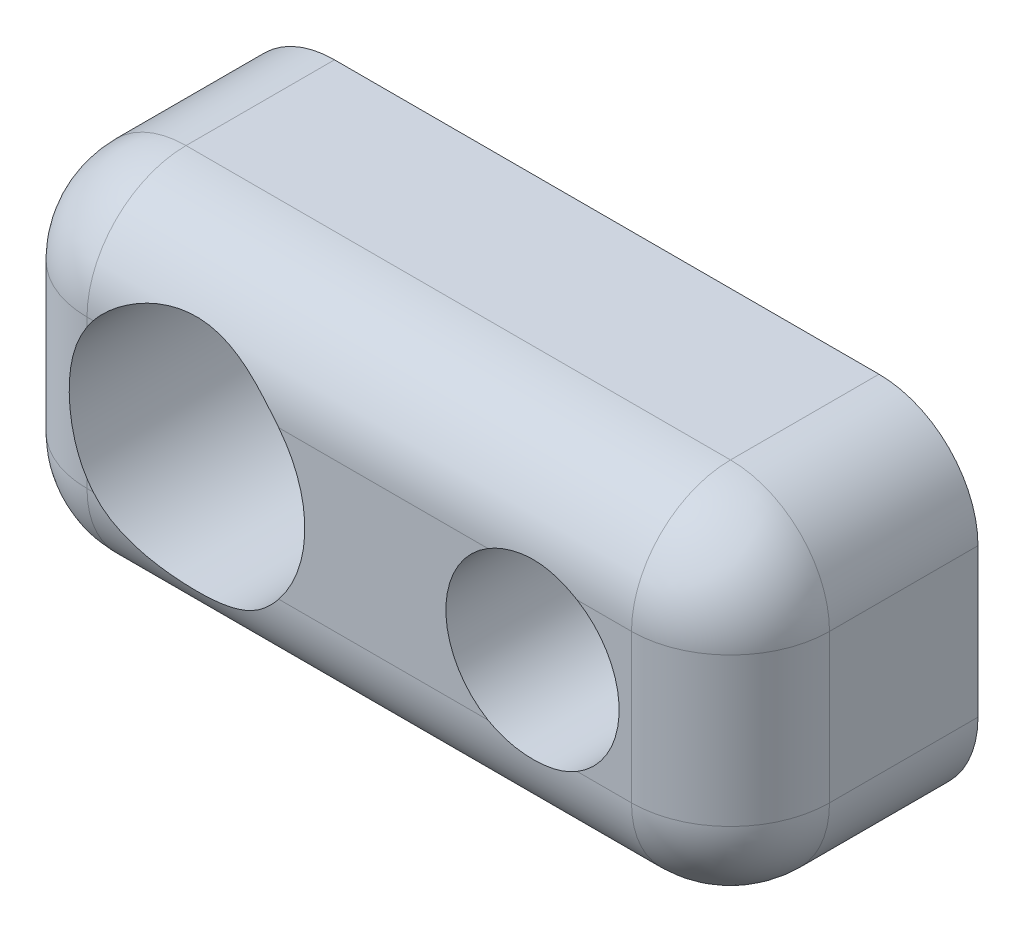
SolidWorks part; units mm, degrees
ref_plane "Front Plane" through (0, 0, 0) normal (0, 0, 1) x (1, 0, 0)
ref_plane "Top Plane" through (0, 0, 0) normal (0, 1, 0) x (1, 0, 0)
ref_plane "Right Plane" through (0, 0, 0) normal (1, 0, 0) x (0, 0, -1)
sketch "Sketch1" plane through (0, 0, 0) normal (0, 0, 1) x (1, 0, 0)
  line L0 (-3.5, 0) -> (3.5, 0) construction
  line L1 (-5.5, 3.5) -> (5.5, 3.5)
  line L2 (-7.5, 1.5) -> (-7.5, -1.5)
  line L3 (-5.5, -3.5) -> (5.5, -3.5)
  line L4 (7.5, 1.5) -> (7.5, -1.5)
  line L5 (-7.5, 3.5) -> (7.5, -3.5) construction
  line L6 (-7.5, -3.5) -> (7.5, 3.5) construction
  circle A0 centre (-3.5, 0) radius 2.4
  circle A1 centre (3.5, 0) radius 1.75
  arc A2 (5.5, 3.5) -> (7.5, 1.5) centre (5.5, 1.5) cw
  arc A3 (5.5, -3.5) -> (7.5, -1.5) centre (5.5, -1.5) ccw
  arc A4 (-7.5, -1.5) -> (-5.5, -3.5) centre (-5.5, -1.5) ccw
  arc A5 (-5.5, 3.5) -> (-7.5, 1.5) centre (-5.5, 1.5) ccw
  point P0 (0, 0)
  point P10 (0, 0)
  dimension "D3" = 4.8
  dimension "D5" = 2
  dimension "D6" = 3.5
  dimension "D1" = 7
  dimension "D2" = 15
  dimension "D4" = 4
extrude "Boss-Extrude1" add sketch "Sketch1" along normal blind 5
fillet "Fillet1" radius 2 8 edges at (6.9142, 2.9142, 5) (7.5, 0, 5) (6.9142, -2.9142, 5) (0, -3.5, 5) (-6.9142, -2.9142, 5) (-7.5, 0, 5) (-6.9142, 2.9142, 5) (0, 3.5, 5)
